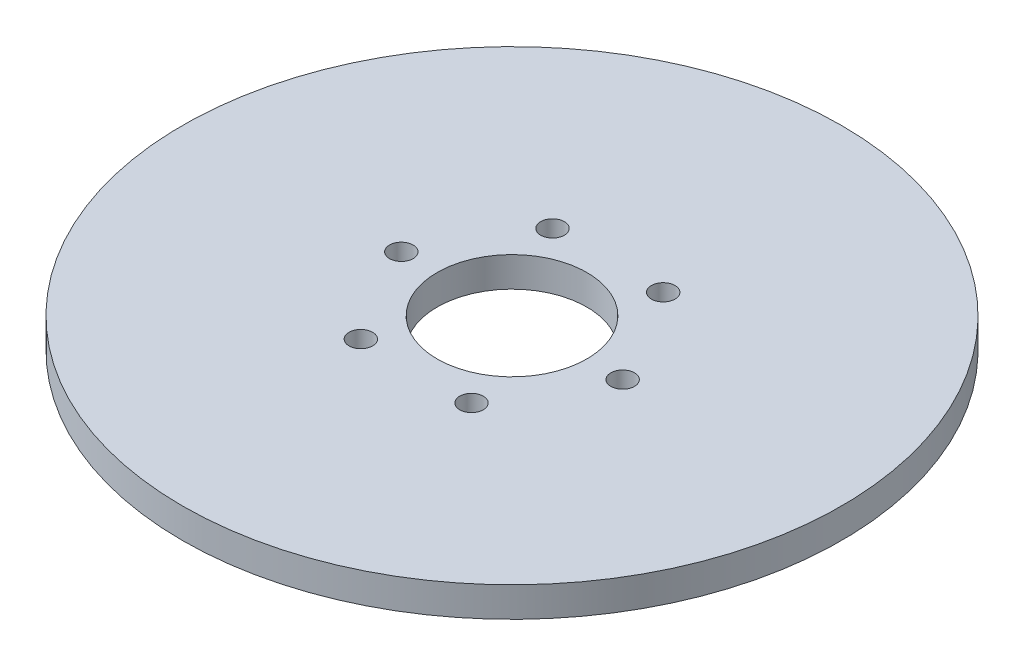
SolidWorks part; units mm, degrees
ref_plane "Front Plane" through (0, 0, 0) normal (0, 0, 1) x (1, 0, 0)
ref_plane "Top Plane" through (0, 0, 0) normal (0, 1, 0) x (1, 0, 0)
ref_plane "Right Plane" through (0, 0, 0) normal (1, 0, 0) x (0, 0, -1)
sketch "Sketch1" plane through (0, 0, 0) normal (0, 1, 0) x (1, 0, 0)
  circle A0 centre (0, 0) radius 55
  dimension "FLANGE_OD" = 110
extrude "Boss-Extrude1" add sketch "Sketch1" along normal blind 5
sketch "Sketch2" plane through (0, 0, 0) normal (0, 1, 0) x (1, 0, 0)
  circle A0 centre (0, 0) radius 12.5
  dimension "BORE_D" = 25
extrude "Cut-Extrude1" cut sketch "Sketch2" along normal through all
sketch "Sketch3" plane through (0, 5, 0) normal (0, 1, 0) x (1, 0, 0)
  circle A0 centre (0, 0) radius 18.4687 construction
  circle A1 centre (-18.4687, 0) radius 1.9724
  dimension "BOLT_D" = 3.9448
  dimension "BOLT_PCD" = 36.9375
extrude "Cut-Extrude2" cut sketch "Sketch3" against normal blind 3.3063
pattern_circular "CirPattern1" count 6 over 360 about axis through (0, 0, 0) along (0, 1, 0) of "Cut-Extrude2"
